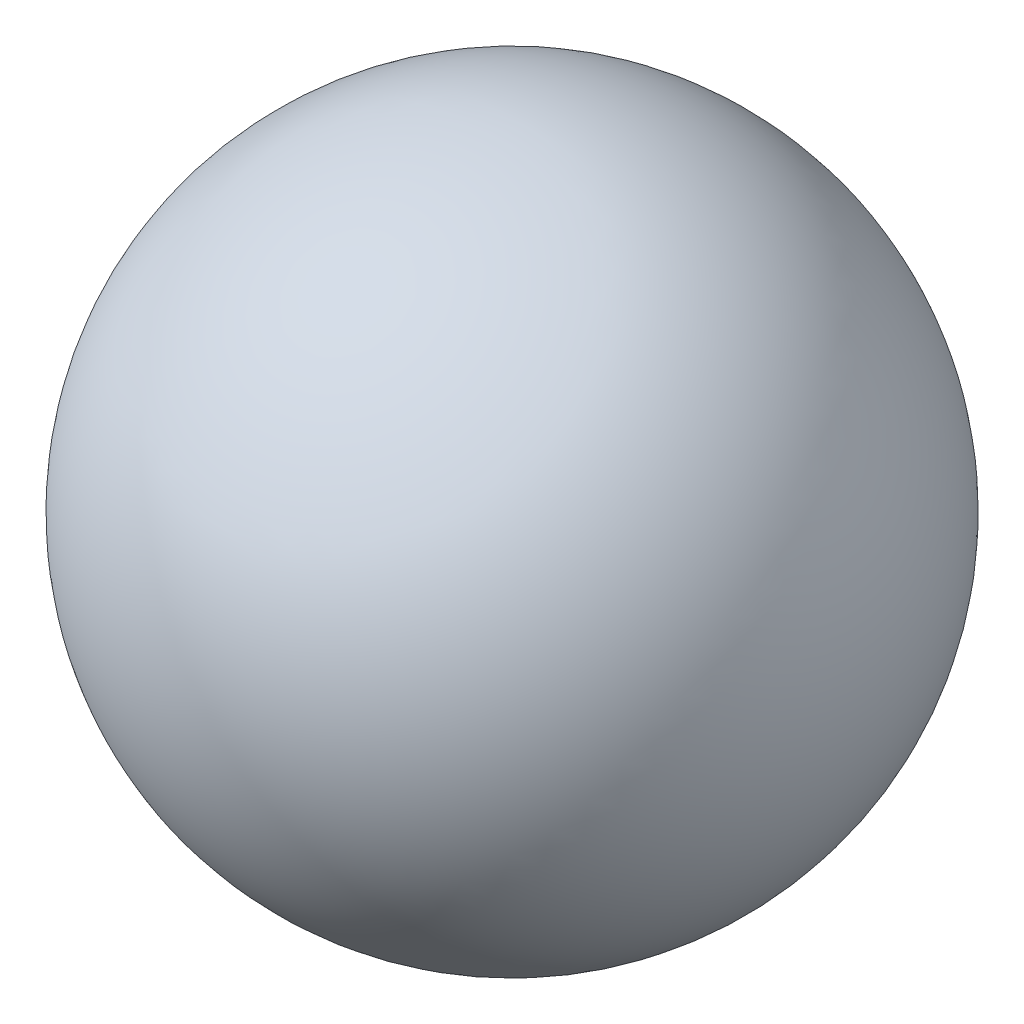
SolidWorks part; units mm, degrees
ref_plane "Front Plane" through (0, 0, 0) normal (0, 0, 1) x (1, 0, 0)
ref_plane "Top Plane" through (0, 0, 0) normal (0, 1, 0) x (1, 0, 0)
ref_plane "Right Plane" through (0, 0, 0) normal (1, 0, 0) x (0, 0, -1)
sketch "Sketch3" plane through (0, 0, 0) normal (0, 1, 0) x (1, 0, 0)
  line L0 (0, 0) -> (-5, 0) construction
  line L1 (-5, 0) -> (-5, -90)
  line L3 (0, -90) -> (0, 0) construction
  line L4 (-5, -90) -> (-36.8791, -90)
  line L8 (0, -90) -> (-5, -90) construction
  line L9 (0, -90) -> (0, -135) construction
  line L10 (0, -135) -> (0, -242) construction
  line L11 (16, -200.5) -> (16, -253.5) construction
  line L12 (0, -242) -> (107, -242) construction
  line L13 (107, -242) -> (216, -242) construction
  line L14 (0, -242) -> (0, -200.5) construction
  line L15 (232, -226) -> (200, -226)
  line L16 (232, -226) -> (232, -258)
  line L17 (232, -258) -> (200, -258)
  line L18 (200, -226) -> (200, -258)
  line L19 (232, -226) -> (200, -258) construction
  line L20 (232, -258) -> (200, -226) construction
  line L21 (16, -200.5) -> (-16, -200.5) construction
  line L22 (-16, -200.5) -> (-16, -253.5) construction
  line L23 (-16, -253.5) -> (16, -253.5) construction
  line L24 (0, -474) -> (0, -242) construction
  line L25 (-36.8791, -55) -> (-5, -55)
  line L26 (-339, -135) -> (339, -135) construction
  circle A0 centre (0, -135) radius 11.5
  circle A1 centre (0, -242) radius 11.5 construction
  circle A2 centre (107, -242) radius 11.5
  circle A8 centre (0, -242) radius 232 construction
  circle A9 centre (0, -135) radius 339 construction
  point P8 (0, -474)
  point P27 (0, -253.5)
  dimension "D3" = 23
  dimension "D9" = 53
  dimension "D1" = 45
  dimension "D2" = 107
  dimension "D4" = 107
  dimension "D5" = 109
  dimension "D6" = 32
  dimension "D7" = 35
  dimension "D8" = 32
  dimension "D10" = 32
  dimension "D12" = 10
ref_plane "Plane1" through (0, 0, 90) normal (0, 0, 1) x (1, 0, 0)
sketch "Sketch4" plane through (0, 0, 90) normal (0, 0, 1) x (1, 0, 0)
  line L0 (0, 18) -> (-40, 18)
  line L1 (18, 0) -> (-40, 0) construction
  line L2 (-36.8791, 0) -> (-5, 0) construction
  line L3 (-40, -18) -> (-40, 18)
  line L4 (0, -18) -> (-40, -18)
  line L5 (0, 0) -> (107, 0) construction
  arc A0 (0, -18) -> (0, 18) centre (0, 0) ccw
  circle A1 centre (0, 0) radius 5
  dimension "D1" = 36
  dimension "D2" = 58
extrude "Boss-Extrude1" add sketch "Sketch4" against normal up to vertex (35 mm away) contours L1 A0 L0 L3 A1 | A0 L1 A1 L3 L4 region at (-13.3191, 8.9186, 90) region at (-13.3191, -8.9186, 90) up to point (-36.8791, 0, 55)
sketch "Sketch5" plane through (0, 0, 55) normal (0, 0, -1) x (-1, 0, 0)
  line L1 (77, -55) -> (-33, -55)
  line L2 (77, -55) -> (77, 55)
  line L3 (77, 55) -> (-33, 55)
  line L4 (-33, -55) -> (-33, 55)
  line L5 (77, -55) -> (-33, 55) construction
  line L6 (77, 55) -> (-33, -55) construction
  line L7 (-18, 0) -> (-33, 0) construction
  arc A0 (0, 18) -> (0, -18) centre (0, 0) ccw construction
  arc A1 (0, 18) -> (0, -18) centre (0, 0) ccw construction
  point P0 (22, 0)
  point P7 (-18, 0)
  dimension "D1" = 110
  dimension "D2" = 110
  dimension "D3" = 15
extrude "Boss-Extrude2" add sketch "Sketch5" along normal up to vertex (55 mm away) up to point (-5, 0, 0)
sketch "Sketch7" plane through (0, 0, 0) normal (0, 0, -1) x (-1, 0, 0)
  line L4 (87, -65) -> (125, -79.9256)
  line L5 (125, -79.9256) -> (125, 79.9256)
  line L6 (232, 0) -> (-232, 0) construction
  line L7 (125, 0) -> (-43, 0) construction
  line L8 (-43, 65) -> (-43, -65)
  line L9 (-43, -65) -> (87, -65)
  line L10 (87, -65) -> (87, 65)
  line L11 (87, 65) -> (-43, 65)
  line L12 (-43, 65) -> (-43, -65)
  line L13 (-43, -65) -> (87, -65)
  line L15 (87, 65) -> (-43, 65)
  line L16 (87, 65) -> (125, 79.9256)
  dimension "D2" = 125
  dimension "D1" = 10
extrude "Boss-Extrude3" add sketch "Sketch7" against normal blind 10 contours L5 L16 L15 L12 L13 L4
fillet "Fillet1" radius 20 6 edges at (-87, 65, 5) (-125, 79.9256, 5) (43, 65, 5) (43, -65, 5) (-87, -65, 5) (-125, -79.9256, 5)
fillet "Fillet4" radius 10 14 edges at (-22, 55, 10) (-77, 0, 10) (33, 0, 10) (-77, -55, 32.5) (-22, -55, 55) (33, -55, 32.5) (-22, -55, 10) (-22, 55, 55) (-77, 0, 55) (33, 0, 55) (-40, 18, 72.5) (-40, -18, 72.5) (33, 55, 32.5) (-77, 55, 32.5)
sketch "Sketch8" plane through (0, 0, 0) normal (0, 1, 0) x (1, 0, 0)
  line L0 (0, -474) -> (0, 204)
  circle A0 centre (0, -135) radius 339 construction
  arc A1 (0, -474) -> (0, 204) centre (0, -135) ccw
revolve "Revolve1" add sketch "Sketch8" angle 360 about L0 region at (143.8761, 0, 135)
